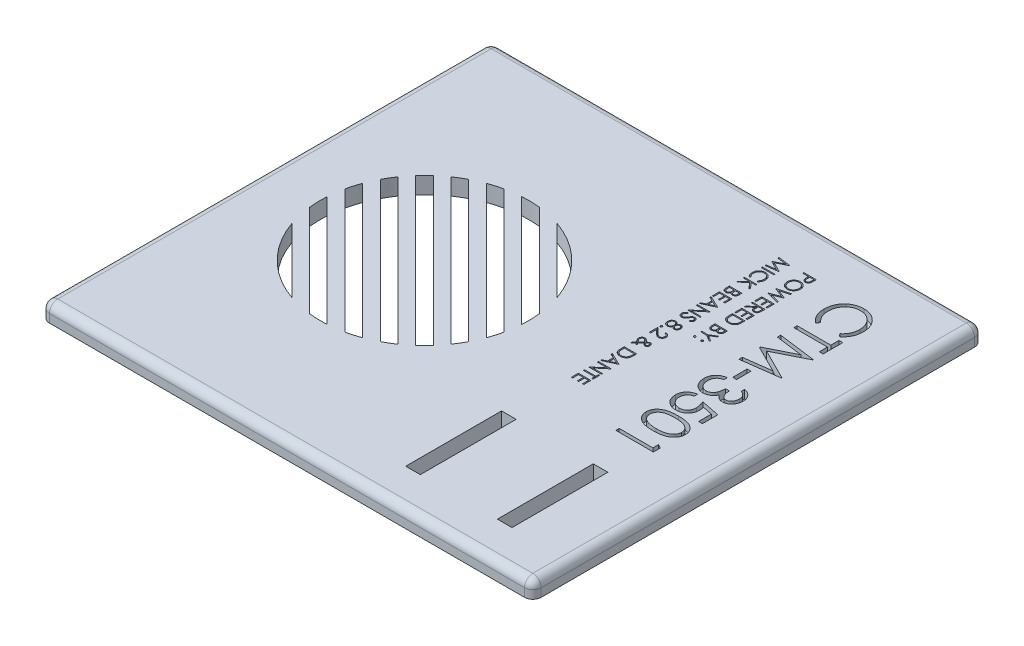
SolidWorks part; units mm, degrees
ref_plane "Front Plane" through (0, 0, 0) normal (0, 0, 1) x (1, 0, 0)
ref_plane "Top Plane" through (0, 0, 0) normal (0, 1, 0) x (1, 0, 0)
ref_plane "Right Plane" through (0, 0, 0) normal (1, 0, 0) x (0, 0, -1)
sketch "Sketch1" plane through (0, 0, 0) normal (0, 1, 0) x (1, 0, 0)
  line L1 (-59, 54) -> (59, 54)
  line L2 (-59, 54) -> (-59, -54)
  line L3 (-59, -54) -> (59, -54)
  line L4 (59, 54) -> (59, -54)
  line L5 (-59, 54) -> (59, -54) construction
  line L6 (-59, -54) -> (59, 54) construction
  point P0 (0, 0)
  dimension "D1" = 118
  dimension "D2" = 108
extrude "Boss-Extrude1" add sketch "Sketch1" along normal blind 4
sketch "Sketch2" plane through (0, 0, 0) normal (0, -1, 0) x (1, 0, 0)
  line L0 (-59, -54) -> (-59, 54) construction
  line L1 (-54, 49) -> (54, 49)
  line L2 (-54, 49) -> (-54, -49)
  line L3 (-54, -49) -> (54, -49)
  line L4 (54, 49) -> (54, -49)
  line L5 (-54, 49) -> (54, -49) construction
  line L6 (-54, -49) -> (54, 49) construction
  line L7 (59, -54) -> (-59, -54) construction
  line L10 (-51, 46) -> (-51, -46)
  line L11 (-51, -46) -> (51, -46)
  line L12 (51, 46) -> (51, -46)
  line L13 (-51, 46) -> (51, 46)
  point P0 (0, 0)
  dimension "D1" = 5
  dimension "D2" = 5
  dimension "D3" = 3
extrude "Boss-Extrude2" add sketch "Sketch2" along normal blind 4
sketch "Sketch3" plane through (0, 4, 0) normal (0, 1, 0) x (1, 0, 0)
  line L0 (-59, -54) -> (59, -54) construction
  line L1 (41.5, -22) -> (45, -22)
  line L2 (41.5, -22) -> (41.5, -45)
  line L3 (41.5, -45) -> (45, -45)
  line L4 (45, -22) -> (45, -45)
  line L5 (41.5, -22) -> (45, -45) construction
  line L6 (41.5, -45) -> (45, -22) construction
  line L7 (23, -45) -> (19.5, -45)
  line L8 (23, -45) -> (23, -22)
  line L9 (23, -22) -> (19.5, -22)
  line L10 (19.5, -45) -> (19.5, -22)
  line L11 (23, -45) -> (19.5, -22) construction
  line L12 (23, -22) -> (19.5, -45) construction
  line L13 (59, -54) -> (59, 54) construction
  point P0 (43.25, -33.5)
  point P5 (21.25, -33.5)
  point P10 (21.25, -45)
  dimension "D1" = 23
  dimension "D2" = 23
  dimension "D3" = 22
  dimension "D4" = 3.5
  dimension "D5" = 3.5
  dimension "D6" = 9
  dimension "D7" = 9
  dimension "D8" = 14
extrude "Cut-Extrude1" cut sketch "Sketch3" against normal up to surface (4 mm away) up to face at (0, 0, 0)
sketch "Sketch4" plane through (0, -4, 0) normal (0, -1, 0) x (1, 0, 0)
  line L0 (54, 49) -> (-54, 49) construction
  line L1 (14.2969, 49) -> (51, 49)
  line L2 (14.2969, 49) -> (14.2969, 8.1946)
  line L3 (14.2969, 8.1946) -> (51, 8.1946)
  line L4 (51, 49) -> (51, 8.1946)
  line L5 (51, -46) -> (51, 46) construction
extrude "Cut-Extrude2" cut sketch "Sketch4" against normal up to surface (4 mm away) up to face at (21.25, 0, 33.5)
sketch "Sketch5" plane through (0, 4, 0) normal (0, 1, 0) x (1, 0, 0)
  line L0 (45, -22) -> (-59, -22) construction
  line L1 (-59, 54) -> (-59, -54) construction
  line L2 (-59, -22) -> (59, -22) construction
  line L3 (59, -54) -> (59, 54) construction
  line L4 (59, -22) -> (59, 54) construction
  line L5 (-21, 0) -> (4, 0) construction
  line L6 (-37.1198, 13.9985) -> (-39.7065, 16.5852)
  line L7 (4, -25) -> (-21, 0) construction
  line L8 (-21, 0) -> (-43.9379, 22.9379) construction
  line L9 (-39.7065, 16.5852) -> (-4.4148, -18.7065)
  line L10 (-37.5852, 18.7065) -> (-2.2935, -16.5852)
  line L11 (-39.7065, 16.5852) -> (-37.5852, 18.7065)
  line L12 (-21, 0) -> (-3.3223, 17.6777) construction
  line L13 (-3.3223, 17.6777) -> (-38.6777, -17.6777) construction
  line L14 (-35.207, 20.5709) -> (-0.4291, -14.207)
  line L15 (-32.5601, 22.1667) -> (1.1667, -11.5601)
  line L16 (-41.5709, 14.207) -> (-6.793, -20.5709)
  line L17 (-43.1667, 11.5601) -> (-9.4399, -22.1667)
  line L18 (-45.4246, 5.3327) -> (-15.6673, -24.4246)
  line L19 (-44.4675, 8.6183) -> (-12.3817, -23.4675)
  line L20 (-29.6183, 23.4675) -> (2.4675, -8.6183)
  line L21 (-26.3327, 24.4246) -> (3.4246, -5.3327)
  line L22 (-45.9479, 1.6134) -> (-19.3866, -24.9479)
  line L23 (-22.6134, 24.9479) -> (3.9479, -1.6134)
  line L24 (-45.8509, -2.7263) -> (-23.7263, -24.8509)
  line L25 (-18.2737, 24.8509) -> (3.8509, 2.7263)
  line L26 (-44.6154, -8.2044) -> (-29.2044, -23.6154)
  line L27 (-12.7956, 23.6154) -> (2.6154, 8.2044)
  line L28 (-39.109, 17.1827) -> (-39.7065, 16.5852)
  line L29 (-5.1173, -18.004) -> (-4.4148, -18.7065)
  line L31 (-59, -54) -> (59, -54) construction
  arc A0 (-44.6154, -8.2044) -> (-29.2044, -23.6154) centre (-21, 0) ccw
  arc A1 (-45.9479, 1.6134) -> (-45.8509, -2.7263) centre (-21, 0) ccw
  arc A2 (-44.4675, 8.6183) -> (-45.4246, 5.3327) centre (-21, 0) ccw
  arc A3 (-41.5709, 14.207) -> (-43.1667, 11.5601) centre (-21, 0) ccw
  arc A4 (-37.5852, 18.7065) -> (-39.7065, 16.5852) centre (-21, 0) ccw
  arc A5 (-32.5601, 22.1667) -> (-35.207, 20.5709) centre (-21, 0) ccw
  arc A6 (-26.3327, 24.4246) -> (-29.6183, 23.4675) centre (-21, 0) ccw
  arc A7 (-23.7263, -24.8509) -> (-19.3866, -24.9479) centre (-21, 0) ccw
  arc A8 (-15.6673, -24.4246) -> (-12.3817, -23.4675) centre (-21, 0) ccw
  arc A9 (-9.4399, -22.1667) -> (-6.793, -20.5709) centre (-21, 0) ccw
  arc A10 (-4.4148, -18.7065) -> (-2.2935, -16.5852) centre (-21, 0) ccw
  arc A11 (-0.4291, -14.207) -> (1.1667, -11.5601) centre (-21, 0) ccw
  arc A12 (2.4675, -8.6183) -> (3.4246, -5.3327) centre (-21, 0) ccw
  arc A13 (3.9479, -1.6134) -> (3.8509, 2.7263) centre (-21, 0) ccw
  arc A14 (2.6154, 8.2044) -> (-12.7956, 23.6154) centre (-21, 0) ccw
  arc A15 (-18.2737, 24.8509) -> (-22.6134, 24.9479) centre (-21, 0) ccw
  dimension "D1" = 50
  dimension "D2" = 25
  dimension "D3" = 3
  dimension "D4" = 1.5
  dimension "D5" = 3
  dimension "D6" = 3
  dimension "D7" = 3
  dimension "D8" = 3
  dimension "D9" = 3
  dimension "D10" = 3
  dimension "D11" = 3
  dimension "D12" = 3
  dimension "D13" = 3
  dimension "D14" = 3
  dimension "D15" = 3
  dimension "D16" = 3
  dimension "D17" = 3
  dimension "D18" = 3
  dimension "D19" = 38
  dimension "D20" = 54
extrude "Cut-Extrude3" cut sketch "Sketch5" against normal up to surface (4 mm away) contours L26 A0 | L24 A7 L22 A1 | L18 A8 L19 A2 | L17 A9 L16 A3 | L14 A11 L15 A5 | L20 A12 L21 A6 | L25 A15 L23 A13 | L9 A10 L10 L11 L6 | A14 L27 region at (-20.9894, 4, 0.0106) region at (-16.7628, 4, -4.2372) region at (-25.2372, 4, 4.2372) region at (-29.472, 4, 8.472) region at (-12.528, 4, -8.472) region at (-33.696, 4, 12.696) region at (-8.304, 4, -12.696) region at (-37.6201, 4, 16.6201) up to face at (2.8594, 0, 9.8)
sketch "Sketch6" plane through (0, 4, 0) normal (0, 1, 0) x (1, 0, 0)
  line L0 (59, -54) -> (59, 54) construction
  line L1 (37.255, 43.3941) -> (52.3509, 43.3941)
  line L2 (37.255, 43.3941) -> (37.255, -8.7394)
  line L3 (37.255, -8.7394) -> (52.3509, -8.7394)
  line L4 (52.3509, 43.3941) -> (52.3509, -8.7394)
  line L5 (17.6967, 43.3941) -> (27, 43.3941)
  line L6 (17.6967, 43.3941) -> (17.6967, -13.8299)
  line L7 (17.6967, -13.8299) -> (27, -13.8299)
  line L8 (27, 43.3941) -> (27, -13.8299)
  dimension "D1" = 32
sketch "Sketch7" plane through (0, 4, 0) normal (0, 1, 0) x (1, 0, 0)
  text T0 "CTM-3501" font "Century Gothic" height 9
sketch "Sketch8" plane through (0, 4, 0) normal (0, 1, 0) x (1, 0, 0)
  text T0 "POWERED BY:\r\nMICK BEANS 8.2 & DANTE" font "Century Gothic" height 3
extrude "Cut-Extrude4" cut sketch "Sketch7" against normal blind 2
extrude "Cut-Extrude5" cut sketch "Sketch8" against normal blind 2
fillet "Fillet1" radius 2 7 edges at (54, -2, -49) (-54, -2, -49) (-54, -2, 49) (-59, 2, 54) (59, 2, 54) (59, 2, -54) (-59, 2, -54)
fillet "Fillet2" radius 2 8 edges at (58.4142, 4, -53.4142) (59, 4, 0) (58.4142, 4, 53.4142) (0, 4, 54) (-58.4142, 4, 53.4142) (-59, 4, 0) (-58.4142, 4, -53.4142) (0, 4, -54)
